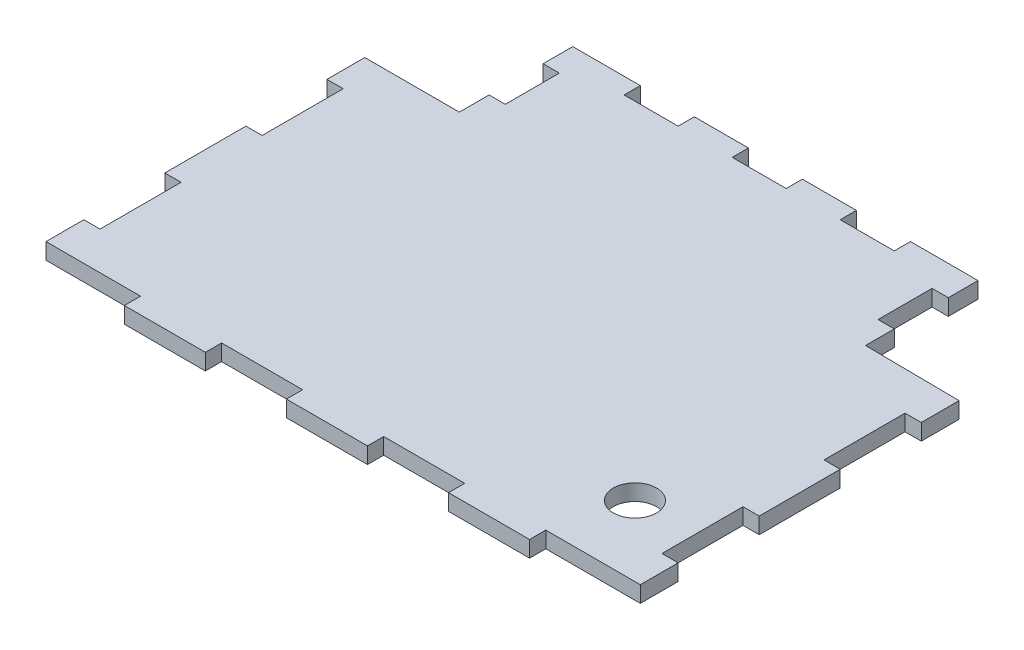
SolidWorks part; units mm, degrees
ref_plane "Alzado" through (0, 0, 0) normal (0, 0, 1) x (1, 0, 0)
ref_plane "Planta" through (0, 0, 0) normal (0, 1, 0) x (1, 0, 0)
ref_plane "Vista lateral" through (0, 0, 0) normal (1, 0, 0) x (0, 0, -1)
sketch "Croquis1" plane through (0, 0, 0) normal (0, 1, 0) x (1, 0, 0)
  line L0 (0, 3) -> (0, 10)
  line L1 (17.5, 0) -> (32.5, 0)
  line L2 (0, 62) -> (17.5, 62)
  line L3 (17.5, 62) -> (17.5, 67.5)
  line L4 (55, 0) -> (62.5, 0)
  line L5 (17.5, 83) -> (30, 83)
  line L6 (50, 80) -> (60, 80)
  line L7 (110, 62) -> (92.5, 62.1878)
  line L8 (110, 3) -> (110, 10)
  line L9 (62.5, 0) -> (62.5, 3)
  line L10 (62.5, 3) -> (77.5, 3)
  line L11 (77.5, 3) -> (77.5, 0)
  line L12 (77.5, 0) -> (92.5, 0)
  line L13 (92.5, 0) -> (92.5, 3)
  line L14 (92.5, 3) -> (110, 3)
  line L15 (20.5, 72.5) -> (20.5, 77.5)
  line L16 (17.5, 3) -> (0, 3)
  line L17 (17.5, 0) -> (17.5, 3)
  line L18 (32.5, 3) -> (32.5, 0)
  line L19 (47.5, 3) -> (32.5, 3)
  line L20 (47.5, 0) -> (47.5, 3)
  line L21 (110, 3) -> (110, 10)
  line L22 (110, 32.5) -> (110, 25)
  line L23 (110, 25) -> (107, 25)
  line L24 (107, 25) -> (107, 10)
  line L25 (107, 10) -> (110, 10)
  line L26 (0, 40) -> (3, 40)
  line L27 (107, 55) -> (110, 55)
  line L28 (107, 40) -> (107, 55)
  line L29 (110, 40) -> (107, 40)
  line L30 (3, 40) -> (3, 55)
  line L31 (3, 55) -> (0, 55)
  line L32 (3, 10) -> (0, 10)
  line L33 (3, 25) -> (3, 10)
  line L34 (0, 25) -> (3, 25)
  line L36 (20.5, 72.5) -> (20.5, 67.5)
  line L37 (20.5, 77.5) -> (17.5, 77.5)
  line L38 (20.5, 67.5) -> (17.5, 67.5)
  line L39 (17.5, 77.5) -> (17.5, 83)
  line L40 (70, 83) -> (60, 83)
  line L41 (50, 80) -> (50, 83)
  line L42 (50, 83) -> (40, 83)
  line L43 (40, 83) -> (40, 80)
  line L44 (40, 80) -> (30, 80)
  line L45 (30, 80) -> (30, 83)
  line L46 (80, 80) -> (80, 83)
  line L47 (70, 80) -> (80, 80)
  line L48 (70, 83) -> (70, 80)
  line L49 (60, 83) -> (70, 83)
  line L50 (60, 80) -> (60, 83)
  line L51 (92.5, 77.5) -> (92.5, 83)
  line L52 (89.5, 67.5) -> (92.5, 67.5)
  line L53 (89.5, 77.5) -> (92.5, 77.5)
  line L54 (40, 83) -> (50, 83)
  line L55 (89.5, 72.5) -> (89.5, 67.5)
  line L56 (89.5, 72.5) -> (89.5, 77.5)
  line L57 (0, 55) -> (0, 62)
  line L58 (0, 25) -> (0, 40)
  line L59 (77.5, 0) -> (92.5, 0)
  line L60 (47.5, 0) -> (62.5, 0)
  line L61 (110, 25) -> (110, 40)
  line L62 (110, 25) -> (110, 32.5)
  line L63 (110, 55) -> (110, 62)
  line L64 (92.5, 83) -> (80, 83)
  line L65 (92.5, 62) -> (92.5, 67.5)
  point P10 (55, 83)
  dimension "D3" = 17.5
  dimension "D4" = 21
  dimension "D5" = 7.5
  dimension "D6" = 3
  dimension "D7" = 15
  dimension "D8" = 15
  dimension "D10" = 7.5
  dimension "D11" = 3
  dimension "D12" = 15
  dimension "D14" = 5
  dimension "D16" = 5
  dimension "D17" = 7
  dimension "D19" = 10
  dimension "D20" = 10
extrude "Saliente-Extruir1" add sketch "Croquis1" along normal blind 3 contours L27 L63 L7 L41 L42 L43 L44 L45 L5 L39 L37 L15 L36 L38 L3 L2 L57 L31 L30 L26 L58 L34 L33 L32 L0 L16 L17 L1 L18 L19 L20 L60 L4 L9 L10 L11 L12 L13 region at (55.009, 0, -39.1128)
sketch "Sketch1" plane through (0, 3, 0) normal (0, 1, 0) x (1, 0, 0)
  line L0 (110, 3) -> (110, 10) construction
  line L1 (77.5, 0) -> (92.5, 0) construction
  circle A0 centre (96, 16) radius 4
  dimension "D1" = 8
  dimension "D2" = 14
  dimension "D3" = 16
extrude "Cut-Extrude1" cut sketch "Sketch1" against normal blind 10 contours A0
